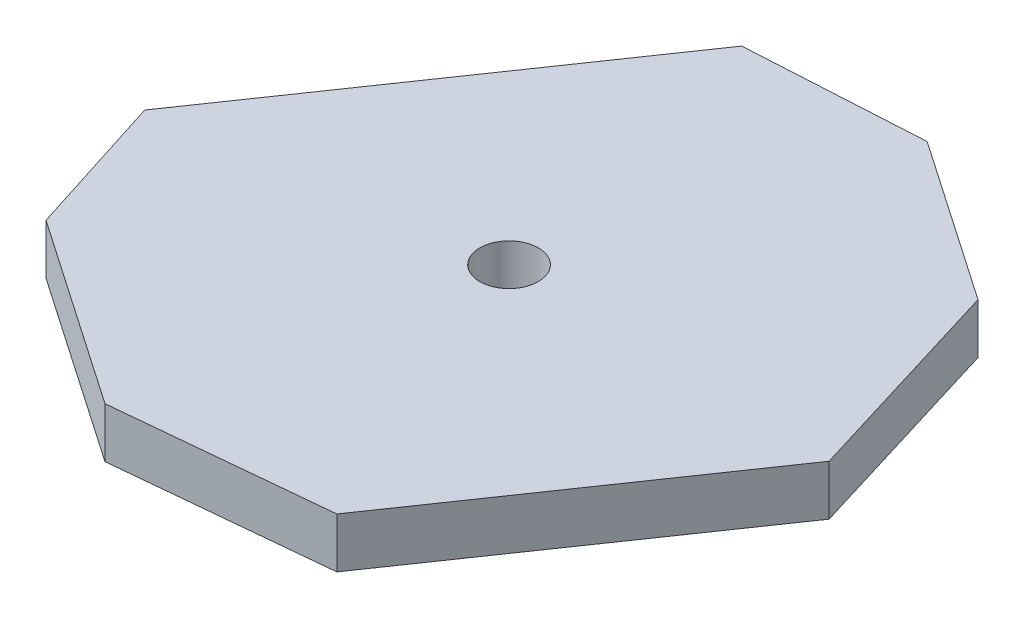
SolidWorks part; units mm, degrees
ref_plane "Спереди" through (0, 0, 0) normal (0, 0, 1) x (1, 0, 0)
ref_plane "Сверху" through (0, 0, 0) normal (0, 1, 0) x (1, 0, 0)
ref_plane "Справа" through (0, 0, 0) normal (1, 0, 0) x (0, 0, -1)
sketch "Эскиз1" plane through (0, 0, 0) normal (0, 1, 0) x (1, 0, 0)
  circle A0 centre (0, 0) radius 9
  circle A1 centre (0, 0) radius 40
extrude "Вытянуть1" add sketch "Эскиз1" along normal blind 13 from offset 7
ref_plane "Плоскость1" through (0, 14.5, 0) normal (0, 1, 0) x (-1, 0, 0)
sketch "Эскиз12" plane through (0, 7, 0) normal (0, -1, 0) x (1, 0, 0)
  circle A0 centre (0, 0) radius 43.0163
  circle A1 centre (0, 0) radius 18
extrude "Вытянуть5" cut sketch "Эскиз12" against normal blind 7
sketch "Эскиз16" plane through (0, 20, 0) normal (0, 1, 0) x (1, 0, 0)
  line L0 (-8.7329, 36.5475) -> (12.2358, 37.7522)
  line L1 (-9.7669, -38.5459) -> (15.5126, -36.1011)
  line L2 (15.5126, -36.1011) -> (39.4775, -1.2135)
  line L3 (39.4775, -1.2135) -> (31.6491, 24.4169)
  line L4 (31.6491, 24.4169) -> (12.2358, 37.7522)
  line L5 (-9.7669, -38.5459) -> (-32.2858, -23.0772)
  line L6 (-7.1915, -44.52) -> (-37.8812, -24.4696)
  line L7 (-37.8812, -24.4696) -> (-45.367, 5.3714)
  line L8 (-45.367, 5.3714) -> (-23.143, 39.388)
  line L9 (-23.143, 39.388) -> (7.6403, 44.5959)
  line L10 (37.7704, 24.9111) -> (7.6403, 44.5959)
  line L11 (0, 0) -> (36.6838, 56.1494) construction
  line L12 (46.1513, -5.8577) -> (37.7704, 24.9111)
  line L13 (-37.7976, -5.7643) -> (-8.7329, 36.5475)
  line L14 (-32.2858, -23.0772) -> (-37.7976, -5.7643)
  line L15 (23.1156, -39.3926) -> (46.1513, -5.8577)
  line L16 (-7.1915, -44.52) -> (23.1156, -39.3926)
  line L17 (12.2358, 37.7522) -> (-51.8228, 34.0718) construction
extrude "Вырез-Вытянуть5" cut sketch "Эскиз16" against normal blind 10
sketch "Эскиз17" plane through (0, 20, 0) normal (0, 1, 0) x (1, 0, 0)
  circle A0 centre (0, 0) radius 3.5
  circle A1 centre (0, 0) radius 9
extrude "Вытянуть6" add sketch "Эскиз17" against normal blind 8
fillet "Скругление1" radius 7 1 edges at (0, 14, -18)
